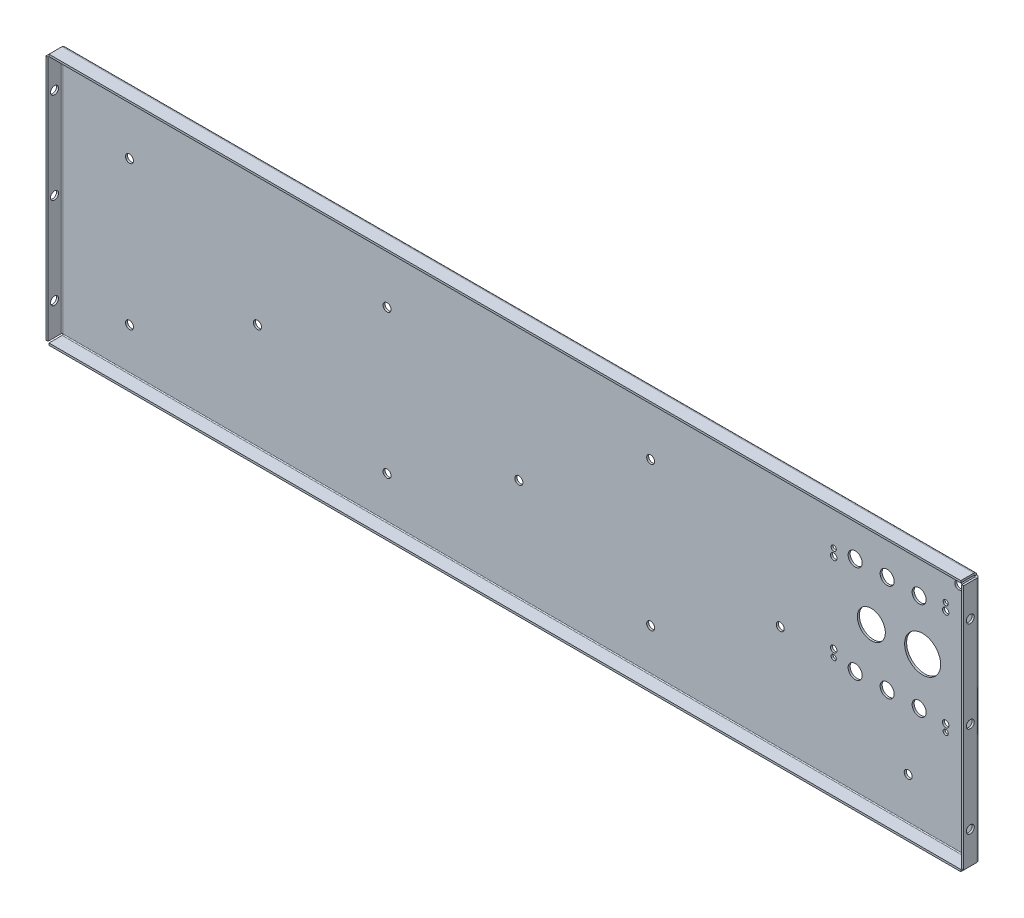
SolidWorks part; units mm, degrees
note: The reader was unsure of these and kept them because the rebuilt part matched: flange length of "Edge-Flange1", "Edge-Flange2", "Edge-Flange3".
material "6061-T6 (SS)"
ref_plane "Front Plane" through (0, 0, 0) normal (0, 0, 1) x (1, 0, 0)
ref_plane "Top Plane" through (0, 0, 0) normal (0, 1, 0) x (1, 0, 0)
ref_plane "Right Plane" through (0, 0, 0) normal (1, 0, 0) x (0, 0, -1)
sketch "Sketch1" plane through (0, 0, 0) normal (0, 0, 1) x (1, 0, 0)
  line L1 (-361.95, -100.076) -> (361.95, -100.076)
  line L2 (-361.95, -100.076) -> (-361.95, 100.076)
  line L3 (-361.95, 100.076) -> (361.95, 100.076)
  line L4 (361.95, -100.076) -> (361.95, 100.076)
  line L5 (-361.95, -100.076) -> (361.95, 100.076) construction
  line L6 (-361.95, 100.076) -> (361.95, -100.076) construction
  point P0 (0, 0)
  dimension "D1" = 200.152
  dimension "D2" = 723.9
base flange "Base-Flange1" sketch "Sketch1" thickness 1.6002 reverse thickness direction no parameters "D1"=0.7366
edge flange "Edge-Flange1" sketch "Sketch8" flange angle 90 flange length 12.7 flange position material inside bend radius 0.7366 thickness 1.6002 relief rectangular parameters "D6"=10
sketch "Sketch8" plane through (0, 100.076, 0) normal (0, 1, 0) x (-1, 0, 0)
  line L0 (-361.95, 0) -> (361.95, 0) construction
  line L1 (-361.95, 0) -> (361.95, 0)
  line L2 (-361.95, 0) -> (-361.95, 11.0998)
  line L3 (-361.95, 11.0998) -> (361.95, 11.0998)
  line L4 (361.95, 11.0998) -> (361.95, 0)
bend "EdgeBend1" bend radius 0.7366 bend angle 90 parameters "D5"=1
edge flange "Edge-Flange2" sketch "Sketch11" flange angle 90 flange length 12.7 flange position material inside bend radius 0.7366 thickness 1.6002 relief rectangular parameters "D6"=10
sketch "Sketch11" plane through (0, -100.076, 0) normal (0, 1, 0) x (-1, 0, 0)
  line L0 (361.95, 0) -> (-361.95, 0) construction
  line L1 (361.95, 0) -> (-361.95, 0)
  line L2 (-361.95, 0) -> (-361.95, 11.0998)
  line L3 (-361.95, 11.0998) -> (361.95, 11.0998)
  line L4 (361.95, 11.0998) -> (361.95, 0)
bend "EdgeBend2" bend radius 0.7366 bend angle 90 parameters "D5"=2
sketch "Sketch12" plane through (0, 0, -1.6002) normal (0, 0, -1) x (-1, 0, 0)
  line L0 (-320.548, 23.2684) -> (-361.95, 23.2684) construction
  line L1 (-361.95, -97.7392) -> (-361.95, 97.7392) construction
  line L2 (-320.548, 23.2684) -> (-207.518, -14.351) construction
  circle A0 centre (-207.518, -14.351) radius 3.175
  circle A1 centre (0, -17.526) radius 3.175
  circle A2 centre (207.518, -14.351) radius 3.175
  circle A3 centre (-207.518, -14.351) radius 3.175 construction
  circle A4 centre (-320.548, 23.2684) radius 20.955 construction
  circle A5 centre (-320.548, 23.2684) radius 14.2875
  circle A21 centre (-207.518, -14.351) radius 101.6 construction
  circle A22 centre (0, -17.526) radius 101.6 construction
  circle A23 centre (207.518, -14.351) radius 101.6 construction
  dimension "D1" = 41.91
  dimension "D24" = 203.2
  dimension "D3" = 28.575
  dimension "D4" = 41.402
  dimension "D5" = 119.126
extrude "Cut-Extrude1" cut sketch "Sketch12" against normal through all normal cut yes
sketch "Sketch13" plane through (0, 0, -108.3564) normal (0, 0, -1) x (-1, 0, 0)
  circle A1 centre (-309.118, -65.151) radius 3.175
  circle A2 centre (-104.6381, -65.151) radius 3.175
  circle A3 centre (-104.6381, 49.149) radius 3.175
  circle A4 centre (104.6381, 49.149) radius 3.175
  circle A5 centre (104.6381, -65.151) radius 3.175
  circle A6 centre (309.118, -65.151) radius 3.175
  circle A7 centre (309.118, 49.149) radius 3.175
extrude "Cut-Extrude2" cut sketch "Sketch13" against normal through all normal cut yes
edge flange "Edge-Flange3" sketch "Sketch18" flange profiles "Sketch18", "Sketch19" flange angle 90 flange length 12.7 flange position bend outside bend radius 0.7366 thickness 1.6002 relief rectangular parameters "D6"=10, "D8"=0.254
sketch "Sketch18" plane through (-361.95, 0, 0) normal (1, 0, 0) x (0, 1, 0)
  line L0 (97.7392, 0) -> (-97.7392, 0) construction
  line L1 (97.7392, 0) -> (-97.7392, 0)
  line L2 (-97.7392, 0) -> (-97.7392, 11.0998)
  line L3 (-97.7392, 11.0998) -> (97.7392, 11.0998)
  line L4 (97.7392, 11.0998) -> (97.7392, 0)
sketch "Sketch19" plane through (361.95, 0, 0) normal (-1, 0, 0) x (0, -1, 0)
  line L1 (97.7392, 0) -> (-97.7392, 0) construction
  line L2 (-97.7392, 0) -> (-97.7392, 11.0998)
  line L3 (-97.7392, 11.0998) -> (97.7392, 11.0998)
  line L4 (97.7392, 11.0998) -> (97.7392, 0)
  line L5 (97.7392, 0) -> (-97.7392, 0)
bend "EdgeBend3" bend radius 0.7366 bend angle 90 parameters "D5"=3
bend "EdgeBend4" bend radius 0.7366 bend angle 90 parameters "D5"=4
sketch "Sketch20" plane through (-364.2868, 0, 0) normal (-1, 0, 0) x (0, 0, 1)
  line L1 (5.9182, 97.7392) -> (5.9182, -97.7392) construction
  line L2 (0.7366, 97.7392) -> (11.0998, 97.7392) construction
  line L3 (11.0998, -97.7392) -> (0.7366, -97.7392) construction
  circle A0 centre (5.9182, 72.3392) radius 3.175
  circle A1 centre (5.9182, 0) radius 3.175
  circle A2 centre (5.9182, -72.3392) radius 3.175
  point P14 (5.9182, 0)
  dimension "D1" = 6.35
  dimension "D2" = 25.4
  dimension "D3" = 25.4
extrude "Cut-Extrude3" cut sketch "Sketch20" against normal through all normal cut yes
sketch "Sketch22" plane through (0, 0, 0) normal (0, 0, 1) x (1, 0, 0)
  line L0 (279.8318, 23.2684) -> (320.548, 23.2684) construction
  line L1 (338.8601, -21.3086) -> (338.8601, -15.4666) construction
  line L2 (338.8601, 62.0034) -> (338.8601, 67.8454) construction
  line L3 (320.548, 23.2684) -> (338.8601, 62.0034) construction
  line L4 (320.548, 23.2684) -> (338.8601, -15.4666) construction
  line L5 (320.548, 23.2684) -> (317.7781, -15.4666) construction
  line L6 (320.548, 23.2684) -> (317.7781, 62.0034) construction
  line L7 (279.8318, 23.2684) -> (292.3781, 62.0034) construction
  line L8 (279.8318, 23.2684) -> (266.9781, 62.0034) construction
  line L9 (279.8318, 23.2684) -> (266.9781, -15.4666) construction
  line L10 (279.8318, 23.2684) -> (292.3781, -15.4666) construction
  line L11 (279.8318, 23.2684) -> (249.9601, -8.4816) construction
  line L12 (249.9601, -14.3236) -> (249.9601, -8.4816) construction
  line L13 (279.8318, 23.2684) -> (249.9601, 55.0184) construction
  line L14 (249.9601, 55.0184) -> (249.9601, 60.8604) construction
  circle A0 centre (279.8318, 23.2684) radius 21 construction
  circle A1 centre (266.9781, -15.4666) radius 5.5562
  circle A2 centre (249.9601, -8.4816) radius 2.5527
  circle A3 centre (249.9601, -14.3236) radius 2.0447
  circle A4 centre (249.9601, 55.0184) radius 2.5527
  circle A5 centre (249.9601, 60.8604) radius 2.0447
  circle A6 centre (266.9781, 62.0034) radius 5.5562
  circle A7 centre (292.3781, 62.0034) radius 5.5563
  circle A8 centre (317.7781, 62.0034) radius 5.5563
  circle A9 centre (338.8601, 62.0034) radius 2.5527
  circle A10 centre (338.8601, 67.8454) radius 2.0447
  circle A11 centre (338.8601, -15.4666) radius 2.5527
  circle A12 centre (338.8601, -21.3086) radius 2.0447
  circle A13 centre (320.548, 23.2684) radius 14.2812 construction
  circle A14 centre (279.8318, 23.2684) radius 11.1061
  circle A15 centre (292.3781, -15.4666) radius 5.5562
  circle A16 centre (317.7781, -15.4666) radius 5.5562
  circle A17 centre (320.548, 23.2684) radius 21 construction
  circle A18 centre (320.548, 23.2684) radius 14.2875 construction
  point P0 (203.3448, 316.475)
  dimension "D15" = 11.1125
  dimension "D17" = 4.0894
  dimension "D19" = 28.5623
  dimension "D1" = 43.5934
  dimension "D2" = 46.746
  dimension "D3" = 5.842
  dimension "D4" = 136.746
  dimension "D5" = 46.746
  dimension "D6" = 24.896
  dimension "D7" = 36.305
  dimension "D8" = 36.305
  dimension "D9" = 24.896
  dimension "D10" = 40.812
  dimension "D11" = 85.91
  dimension "D12" = 85.91
  dimension "D13" = 29.393
  dimension "D14" = 29.393
  dimension "D16" = 38.8339
  dimension "D18" = 5.842
  dimension "D20" = 154.697
  dimension "D21" = 154.697
  dimension "D22" = 136.746
  dimension "D23" = 40.7162
  dimension "D24" = 42.8454
  dimension "D25" = 40.7162
extrude "Cut-Extrude4" cut sketch "Sketch22" against normal through all normal cut yes
sketch "Sketch23" plane through (0, 0, -1.6002) normal (0, 0, -1) x (-1, 0, 0)
  line L2 (361.95, 97.7392) -> (-361.95, 97.7392) construction
  line L4 (-361.95, -97.7392) -> (-361.95, 97.7392) construction
  circle A0 centre (-349.25, 85.0392) radius 3.175
  dimension "D1" = 6.35
  dimension "D2" = 12.7
  dimension "D3" = 12.7
extrude "Cut-Extrude5" cut sketch "Sketch23" against normal through all normal cut yes
sketch "Bend-Lines1" [suppressed] plane through (0, 0, 0) normal (0, 1, 0) x (1, 0, 0)
sketch "Bounding-Box1" [suppressed] plane through (0, 0, 0) normal (0, 1, 0) x (1, 0, 0)
sheet metal parameters "Sheet-Metal1" thickness 1.6002 parameters "D1"=0.7366
flat pattern "Flat-Pattern1" [suppressed]
sketch "Bend-Lines2" plane through (0, 0, 0) normal (0, 1, 0) x (1, 0, 0)
sketch3d "Bounding-Box2" [suppressed]
  line L0 (368.3, -100.076, 0) -> (-368.3, -100.076, 0) construction
  line L1 (368.3, 100.076, 0) -> (-368.3, 100.076, 0) construction
  line L2 (368.3, -100.076, 0) -> (368.3, 100.076, 0) construction
  line L3 (-368.3, -100.076, 0) -> (-368.3, 100.076, 0) construction
sheet metal parameters "Sheet-Metal2" thickness 1.6002 parameters "D1"=0.7366
flat pattern "Flat-Pattern1"
sketch "Bend-Lines2" plane through (0, 0, 0) normal (0, 0, 1) x (1, 0, 0)
  line L0 (368.3, 98.9461) -> (-368.3, 98.9461) construction
  line L1 (368.3, 98.9461) -> (-368.3, 98.9461) construction
sketch3d "Bounding-Box2" [suppressed]
  line L0 (-368.3, -100.076, 0) -> (368.3, -100.076, 0) construction
  line L1 (-368.3, 158.5222, 0) -> (368.3, 158.5222, 0) construction
  line L2 (-368.3, -100.076, 0) -> (-368.3, 158.5222, 0) construction
  line L3 (368.3, -100.076, 0) -> (368.3, 158.5222, 0) construction
bend of the flat pattern "Flatten-<EdgeBend1>1"
sheet metal parameters "Sheet-Metal3" thickness 1.6002 parameters "D1"=0.7366
flat pattern "Flat-Pattern1"
sketch "Bend-Lines2" plane through (0, 0, 0) normal (0, 0, 1) x (1, 0, 0)
  line L0 (368.3, 98.9461) -> (-368.3, 98.9461) construction
  line L1 (368.3, 98.9461) -> (-368.3, 98.9461) construction
  line L2 (-368.3, -98.9461) -> (368.3, -98.9461) construction
  line L3 (-368.3, -98.9461) -> (368.3, -98.9461) construction
sketch3d "Bounding-Box2" [suppressed]
  line L0 (-368.3, -110.5162, 0) -> (368.3, -110.5162, 0) construction
  line L1 (-368.3, 110.5162, 0) -> (368.3, 110.5162, 0) construction
  line L2 (-368.3, -110.5162, 0) -> (-368.3, 110.5162, 0) construction
  line L3 (368.3, -110.5162, 0) -> (368.3, 110.5162, 0) construction
bend of the flat pattern "Flatten-<EdgeBend1>1"
bend of the flat pattern "Flatten-<EdgeBend2>1"
sheet metal parameters "Sheet-Metal4" thickness 1.6002 parameters "D1"=0.7366
flat pattern "Flat-Pattern1"
sketch "Bend-Lines2" plane through (0, 0, 0) normal (0, 0, 1) x (1, 0, 0)
  line L0 (368.3, 98.9461) -> (-368.3, 98.9461) construction
  line L1 (368.3, 98.9461) -> (-368.3, 98.9461) construction
  line L2 (-368.3, -98.9461) -> (368.3, -98.9461) construction
  line L3 (-368.3, -98.9461) -> (368.3, -98.9461) construction
sketch3d "Bounding-Box2" [suppressed]
  line L0 (-368.3, -110.5162, 0) -> (368.3, -110.5162, 0) construction
  line L1 (-368.3, 110.5162, 0) -> (368.3, 110.5162, 0) construction
  line L2 (-368.3, -110.5162, 0) -> (-368.3, 110.5162, 0) construction
  line L3 (368.3, -110.5162, 0) -> (368.3, 110.5162, 0) construction
bend of the flat pattern "Flatten-<EdgeBend1>1"
bend of the flat pattern "Flatten-<EdgeBend2>1"
sheet metal parameters "Sheet-Metal5" thickness 1.6002 parameters "D1"=0.7366
flat pattern "Flat-Pattern1"
sketch "Bend-Lines2" plane through (0, 0, 0) normal (0, 0, 1) x (1, 0, 0)
  line L0 (368.3, 98.9461) -> (-368.3, 98.9461) construction
  line L1 (368.3, 98.9461) -> (-368.3, 98.9461) construction
  line L2 (-368.3, -98.9461) -> (368.3, -98.9461) construction
  line L3 (-368.3, -98.9461) -> (368.3, -98.9461) construction
sketch3d "Bounding-Box2" [suppressed]
  line L0 (-368.3, -110.5162, 0) -> (368.3, -110.5162, 0) construction
  line L1 (-368.3, 110.5162, 0) -> (368.3, 110.5162, 0) construction
  line L2 (-368.3, -110.5162, 0) -> (-368.3, 110.5162, 0) construction
  line L3 (368.3, -110.5162, 0) -> (368.3, 110.5162, 0) construction
bend of the flat pattern "Flatten-<EdgeBend1>1"
bend of the flat pattern "Flatten-<EdgeBend2>1"
sheet metal parameters "Sheet-Metal6" thickness 1.6002 parameters "D1"=0.7366
flat pattern "Flat-Pattern1"
sketch "Bend-Lines2" plane through (0, 0, 0) normal (0, 0, 1) x (1, 0, 0)
  line L0 (368.3, 98.9461) -> (-368.3, 98.9461) construction
  line L1 (368.3, 98.9461) -> (-368.3, 98.9461) construction
  line L2 (-368.3, -98.9461) -> (368.3, -98.9461) construction
  line L3 (-368.3, -98.9461) -> (368.3, -98.9461) construction
  line L4 (369.5069, -97.7392) -> (369.5069, 97.7392) construction
  line L5 (-369.5069, 97.7392) -> (-369.5069, -97.7392) construction
  line L6 (369.5069, -97.7392) -> (369.5069, 97.7392) construction
  line L7 (-369.5069, 97.7392) -> (-369.5069, -97.7392) construction
sketch3d "Bounding-Box2" [suppressed]
  line L0 (-381.077, -110.5162, 0) -> (381.077, -110.5162, 0) construction
  line L1 (-381.077, 110.5162, 0) -> (381.077, 110.5162, 0) construction
  line L2 (-381.077, -110.5162, 0) -> (-381.077, 110.5162, 0) construction
  line L3 (381.077, -110.5162, 0) -> (381.077, 110.5162, 0) construction
bend of the flat pattern "Flatten-<EdgeBend1>1"
bend of the flat pattern "Flatten-<EdgeBend2>1"
bend of the flat pattern "Flatten-<EdgeBend3>1"
bend of the flat pattern "Flatten-<EdgeBend4>1"
sheet metal parameters "Sheet-Metal7" thickness 1.6002 parameters "D1"=0.7366
flat pattern "Flat-Pattern1"
sketch "Bend-Lines2" plane through (0, 0, 0) normal (0, 0, 1) x (1, 0, 0)
  line L0 (361.95, 98.9461) -> (-361.95, 98.9461) construction
  line L1 (361.95, 98.9461) -> (-361.95, 98.9461) construction
  line L2 (-361.95, -98.9461) -> (361.95, -98.9461) construction
  line L3 (-361.95, -98.9461) -> (361.95, -98.9461) construction
  line L4 (363.1569, -97.7392) -> (363.1569, 97.7392) construction
  line L5 (-363.1569, 97.7392) -> (-363.1569, -97.7392) construction
  line L6 (363.1569, -97.7392) -> (363.1569, 97.7392) construction
  line L7 (-363.1569, 97.7392) -> (-363.1569, -97.7392) construction
sketch3d "Bounding-Box2" [suppressed]
  line L0 (-374.727, -110.5162, 0) -> (374.727, -110.5162, 0) construction
  line L1 (-374.727, 110.5162, 0) -> (374.727, 110.5162, 0) construction
  line L2 (-374.727, -110.5162, 0) -> (-374.727, 110.5162, 0) construction
  line L3 (374.727, -110.5162, 0) -> (374.727, 110.5162, 0) construction
bend of the flat pattern "Flatten-<EdgeBend1>1"
bend of the flat pattern "Flatten-<EdgeBend2>1"
bend of the flat pattern "Flatten-<EdgeBend3>1"
bend of the flat pattern "Flatten-<EdgeBend4>1"
sheet metal parameters "Sheet-Metal8" thickness 1.6002 parameters "D1"=0.7366
flat pattern "Flat-Pattern1"
sketch "Bend-Lines2" plane through (0, 0, 0) normal (0, 0, 1) x (1, 0, 0)
  line L0 (361.95, 98.9461) -> (-361.95, 98.9461) construction
  line L1 (361.95, 98.9461) -> (-361.95, 98.9461) construction
  line L2 (-361.95, -98.9461) -> (361.95, -98.9461) construction
  line L3 (-361.95, -98.9461) -> (361.95, -98.9461) construction
  line L4 (363.1569, -97.7392) -> (363.1569, 97.7392) construction
  line L5 (-363.1569, 97.7392) -> (-363.1569, -97.7392) construction
  line L6 (363.1569, -97.7392) -> (363.1569, 97.7392) construction
  line L7 (-363.1569, 97.7392) -> (-363.1569, -97.7392) construction
sketch3d "Bounding-Box2" [suppressed]
  line L0 (-374.727, -110.5162, 0) -> (374.727, -110.5162, 0) construction
  line L1 (-374.727, 110.5162, 0) -> (374.727, 110.5162, 0) construction
  line L2 (-374.727, -110.5162, 0) -> (-374.727, 110.5162, 0) construction
  line L3 (374.727, -110.5162, 0) -> (374.727, 110.5162, 0) construction
bend of the flat pattern "Flatten-<EdgeBend1>1"
bend of the flat pattern "Flatten-<EdgeBend2>1"
bend of the flat pattern "Flatten-<EdgeBend3>1"
bend of the flat pattern "Flatten-<EdgeBend4>1"
sheet metal parameters "Sheet-Metal9" thickness 1.6002 parameters "D1"=0.7366
flat pattern "Flat-Pattern1"
sketch "Bend-Lines2" plane through (0, 0, 0) normal (0, 0, 1) x (1, 0, 0)
  line L0 (361.95, 98.9461) -> (-361.95, 98.9461) construction
  line L1 (361.95, 98.9461) -> (-361.95, 98.9461) construction
  line L2 (-361.95, -98.9461) -> (361.95, -98.9461) construction
  line L3 (-361.95, -98.9461) -> (361.95, -98.9461) construction
  line L4 (363.1569, -97.7392) -> (363.1569, 97.7392) construction
  line L5 (-363.1569, 97.7392) -> (-363.1569, -97.7392) construction
  line L6 (363.1569, -97.7392) -> (363.1569, 97.7392) construction
  line L7 (-363.1569, 97.7392) -> (-363.1569, -97.7392) construction
sketch3d "Bounding-Box2" [suppressed]
  line L0 (-374.727, -110.5162, 0) -> (374.727, -110.5162, 0) construction
  line L1 (-374.727, 110.5162, 0) -> (374.727, 110.5162, 0) construction
  line L2 (-374.727, -110.5162, 0) -> (-374.727, 110.5162, 0) construction
  line L3 (374.727, -110.5162, 0) -> (374.727, 110.5162, 0) construction
bend of the flat pattern "Flatten-<EdgeBend1>1"
bend of the flat pattern "Flatten-<EdgeBend2>1"
bend of the flat pattern "Flatten-<EdgeBend3>1"
bend of the flat pattern "Flatten-<EdgeBend4>1"
